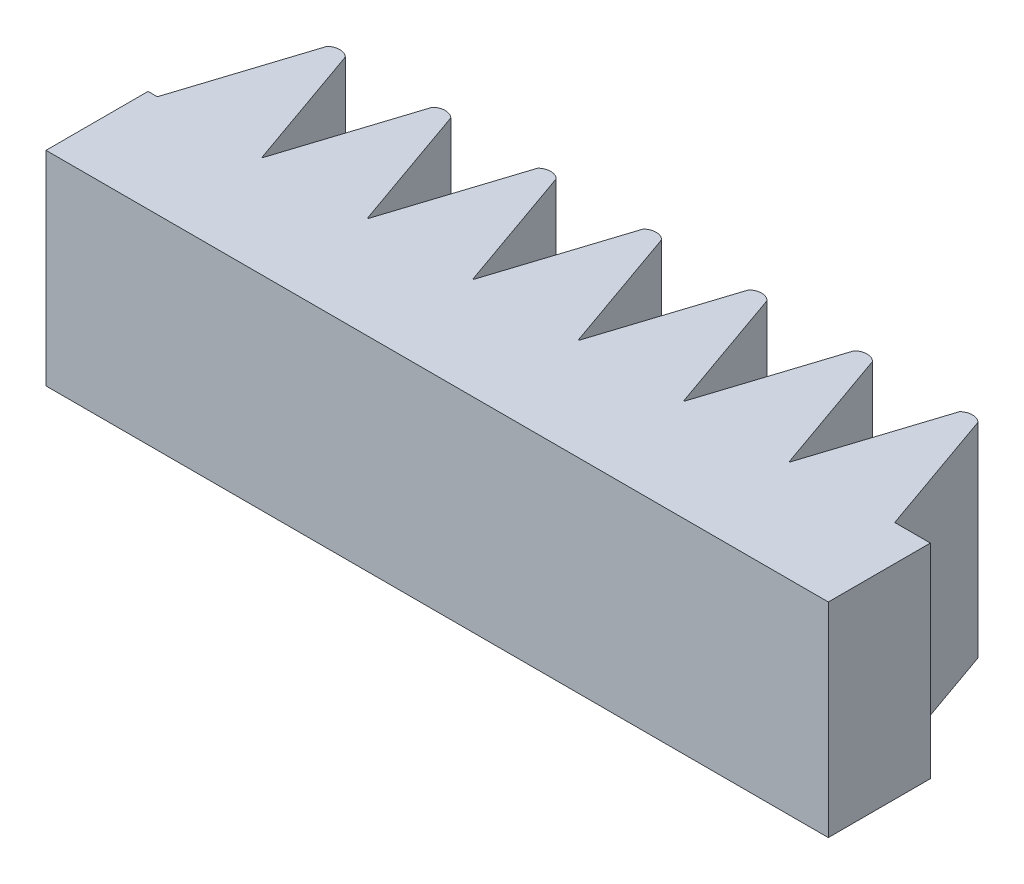
SolidWorks part; units mm, degrees
ref_plane "Front Plane" through (0, 0, 0) normal (0, 0, 1) x (1, 0, 0)
ref_plane "Top Plane" through (0, 0, 0) normal (0, 1, 0) x (1, 0, 0)
ref_plane "Right Plane" through (0, 0, 0) normal (1, 0, 0) x (0, 0, -1)
sketch "Base" plane through (0, 0, 0) normal (0, 1, 0) x (1, 0, 0)
  line L1 (-0.7735, 0) -> (22.2265, 0)
  line L2 (-0.7735, 0) -> (-0.7735, -3)
  line L3 (-0.7735, -3) -> (22.2265, -3)
  line L4 (22.2265, 0) -> (22.2265, -3)
  point P4 (0, -3)
  point P5 (0, 0)
  point P7 (-0.7735, 0)
  dimension "D1" = 23
  dimension "D2" = 3
sketch "Gears-1" plane through (0, 0, 0) normal (0, 1, 0) x (1, 0, 0)
  line L0 (-0.5006, 0) -> (0.7096, 3.7758)
  line L1 (-0.7735, 0) -> (22.2265, 0) construction
  line L2 (0.9805, 3.883) -> (0.9805, 2.653) construction
  line L3 (2.579, 0) -> (1.2514, 3.7758)
  line L4 (-0.5006, 0) -> (2.579, 0)
  line L5 (2.5994, 0) -> (5.679, 0)
  line L6 (5.679, 0) -> (4.3514, 3.7758)
  line L7 (2.5994, 0) -> (3.8096, 3.7758)
  line L8 (5.6994, 0) -> (8.779, 0)
  line L9 (8.779, 0) -> (7.4514, 3.7758)
  line L10 (5.6994, 0) -> (6.9096, 3.7758)
  line L11 (8.7994, 0) -> (11.879, 0)
  line L12 (11.879, 0) -> (10.5514, 3.7758)
  line L13 (8.7994, 0) -> (10.0096, 3.7758)
  line L14 (11.8994, 0) -> (14.979, 0)
  line L15 (14.979, 0) -> (13.6514, 3.7758)
  line L16 (11.8994, 0) -> (13.1096, 3.7758)
  line L17 (14.9994, 0) -> (18.079, 0)
  line L18 (18.079, 0) -> (16.7514, 3.7758)
  line L19 (14.9994, 0) -> (16.2096, 3.7758)
  line L20 (18.0994, 0) -> (21.179, 0)
  line L21 (21.179, 0) -> (19.8514, 3.7758)
  line L22 (18.0994, 0) -> (19.3096, 3.7758)
  arc A0 (0.7096, 3.7758) -> (1.2514, 3.7758) centre (0.9805, 3.4871) cw
  arc A1 (3.8096, 3.7758) -> (4.3514, 3.7758) centre (4.0805, 3.4871) cw
  arc A2 (6.9096, 3.7758) -> (7.4514, 3.7758) centre (7.1805, 3.4871) cw
  arc A3 (10.0096, 3.7758) -> (10.5514, 3.7758) centre (10.2805, 3.4871) cw
  arc A4 (13.1096, 3.7758) -> (13.6514, 3.7758) centre (13.3805, 3.4871) cw
  arc A5 (16.2096, 3.7758) -> (16.7514, 3.7758) centre (16.4805, 3.4871) cw
  arc A6 (19.3096, 3.7758) -> (19.8514, 3.7758) centre (19.5805, 3.4871) cw
  point P10 (1.8493, 1.9221)
  point P40 (1.0517, 2.1735)
  point P41 (2.6035, 0)
  point P42 (1.8146, 2.1475)
  point P43 (2.0487, 2.8757)
  point P44 (2.1826, 3.5515)
  point P45 (1.6065, 3.493)
  point P46 (3.5749, 0)
  point P47 (3.7909, 0)
  point P48 (2.9615, 0)
  point P49 (1.2429, 3.2871)
  point P50 (1.1285, 3.2884)
  point P51 (2.6384, 0)
  point P52 (0.8883, 2.8671)
  point P53 (0.6266, 3.6695)
  point P54 (1.9559, 0)
  point P55 (-0.3704, 0)
  point P56 (2.3946, 0)
  point P57 (1.2514, 3.7758)
  dimension "D1" = 7
extrude "Boss-Extrude1" add sketch "Gears-1" along normal blind 6
extrude "Boss-Extrude2" add sketch "Base" along normal blind 6
